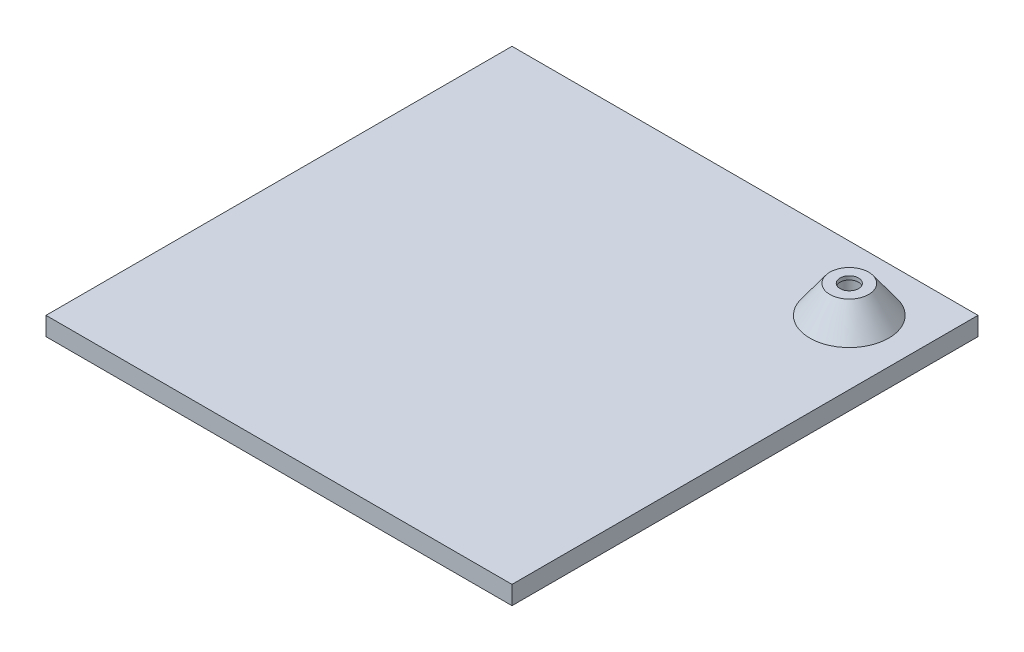
SolidWorks part; units mm, degrees
ref_plane "Front Plane" through (0, 0, 0) normal (0, 0, 1) x (1, 0, 0)
ref_plane "Top Plane" through (0, 0, 0) normal (0, 1, 0) x (1, 0, 0)
ref_plane "Right Plane" through (0, 0, 0) normal (1, 0, 0) x (0, 0, -1)
sketch "Sketch1" plane through (0, 0, 0) normal (0, 1, 0) x (1, 0, 0)
  line L1 (0, 0) -> (126, 0)
  line L2 (0, 0) -> (0, 126)
  line L3 (0, 126) -> (126, 126)
  line L4 (126, 0) -> (126, 126)
  dimension "D1" = 126
  dimension "D2" = 126
extrude "Boss-Extrude1" add sketch "Sketch1" along normal blind 5
sketch "Sketch3" plane through (0, 5, 0) normal (0, 1, 0) x (1, 0, 0)
  line L0 (108.6, 121.1) -> (108.6, 96.1) construction
  circle A0 centre (108.6, 108.6) radius 12.5
extrude "Boss-Extrude2" add sketch "Sketch3" along normal blind 7.5
sketch "Sketch4" plane through (0, 0, 0) normal (0, -1, 0) x (1, 0, 0)
  circle A1 centre (108.6, -108.6) radius 2.95
  dimension "D1" = 5.9
extrude "Cut-Extrude1" cut sketch "Sketch4" against normal blind 11.5
sketch "Sketch6" plane through (0, 12.5, 0) normal (0, 1, 0) x (1, 0, 0)
  line L0 (108.6, 121.1) -> (108.6, 96.1) construction
  circle A0 centre (108.6, 108.6) radius 12.5 construction
  circle A1 centre (108.6, 108.6) radius 2.5
  dimension "D1" = 5
extrude "Cut-Extrude2" cut sketch "Sketch6" against normal through all
chamfer "Chamfer1" distance 10 angle 36 1 edges at (108.6, 12.5, -96.1) first distance on face at (108.6, 12.5, -96.1)
